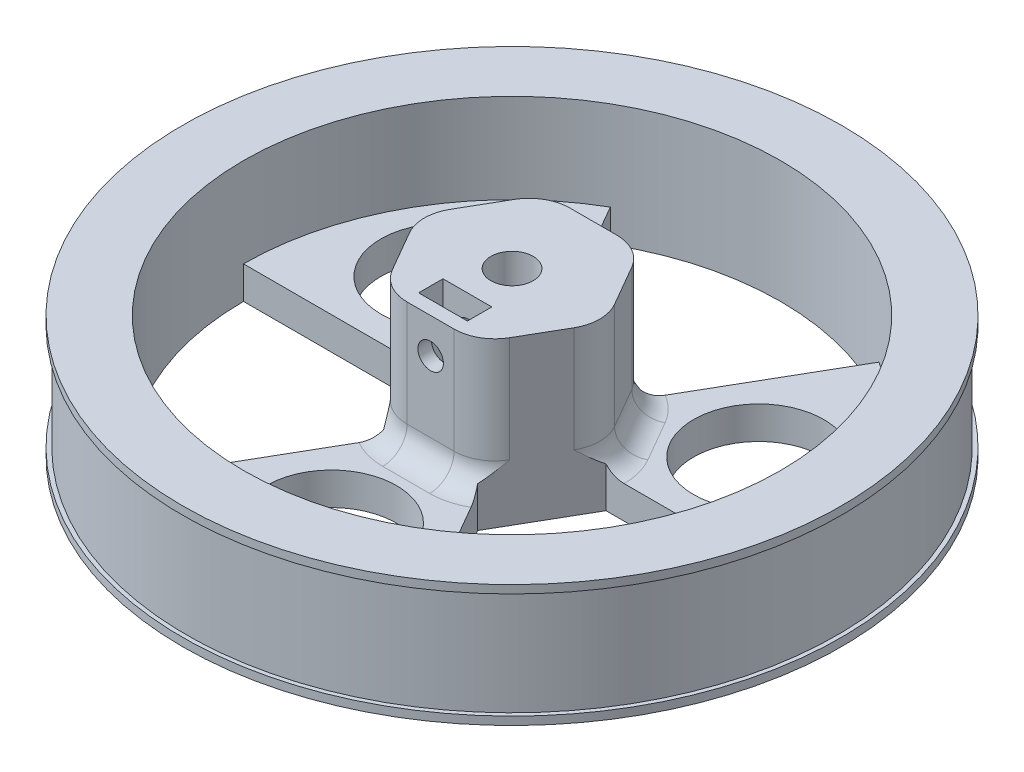
SolidWorks part; units mm, degrees
ref_plane "Front Plane" through (0, 0, 0) normal (0, 0, 1) x (1, 0, 0)
ref_plane "Top Plane" through (0, 0, 0) normal (0, 1, 0) x (1, 0, 0)
ref_plane "Right Plane" through (0, 0, 0) normal (1, 0, 0) x (0, 0, -1)
sketch "Sketch1" plane through (0, 0, 0) normal (0, 1, 0) x (1, 0, 0)
  line L0 (-1.4327, 1.3955) -> (1.21, 1.5925)
  circle A0 centre (0, 0) radius 40.5
  circle A1 centre (0, 0) radius 5
  arc A2 (1.21, 1.5925) -> (-1.4327, 1.3955) centre (0, 0) cw
extrude "Boss-Extrude16" add sketch "Sketch1" along normal blind 5 contours A0 A1 | A1 L0 A2 | A2 L0 region at (-39.3545, 0, 0) region at (-4.8586, 0, 0)
extrude "Boss-Extrude17" add sketch "Sketch1<23>" along normal blind 5 contours A1
sketch "Sketch1<23>" plane through (0, 0, 0) normal (0, 1, 0) x (1, 0, 0) same geometry as "Sketch1"
extrude "Cut-Extrude6" cut sketch "Sketch1<29>" along normal blind 15 contours A2 L0 region at (0.0099, 0, 0.1327)
sketch "Sketch1<29>" plane through (0, 0, 0) normal (0, 1, 0) x (1, 0, 0) same geometry as "Sketch1"
sketch "Sketch13" plane through (0, 5, 0) normal (0, 1, 0) x (1, 0, 0)
  line L0 (-3.828, 6.6303) -> (-19.0526, 33)
  line L1 (38.1051, 0) -> (19.0526, 33)
  line L2 (19.0526, 33) -> (-19.0526, 33)
  line L3 (-19.0526, 33) -> (-38.1051, 0)
  line L4 (-38.1051, 0) -> (-19.0526, -33)
  line L5 (-19.0526, -33) -> (19.0526, -33)
  line L6 (19.0526, -33) -> (38.1051, 0)
  line L7 (7.656, 0) -> (3.828, 6.6303)
  line L8 (3.828, 6.6303) -> (-3.828, 6.6303)
  line L9 (-3.828, 6.6303) -> (-7.656, 0)
  line L10 (-7.656, 0) -> (-3.828, -6.6303)
  line L11 (-3.828, -6.6303) -> (3.828, -6.6303)
  line L12 (3.828, -6.6303) -> (7.656, 0)
  line L13 (-7.656, 0) -> (-38.1051, 0)
  line L14 (-3.828, -6.6303) -> (-19.0526, -33)
  line L15 (3.828, -6.6303) -> (19.0526, -33)
  line L16 (7.656, 0) -> (38.1051, 0)
  line L17 (3.828, 6.6303) -> (19.0526, 33)
  line L18 (19.0526, 33) -> (3.828, 6.6303)
  circle A0 centre (0, 0) radius 33
  circle A1 centre (0, 0) radius 6.6303
extrude "Cut-Extrude7" cut sketch "Sketch13" against normal blind 5 contours L8 L17 L2 L0 region at (0, 5, -21.7812)
extrude "Cut-Extrude8" cut sketch "Sketch13<4>" against normal blind 5 contours L14 L10 L13 L4 region at (-18.8631, 5, 10.8906)
sketch "Sketch13<4>" plane through (0, 5, 0) normal (0, 1, 0) x (1, 0, 0) same geometry as "Sketch13"
extrude "Cut-Extrude9" cut sketch "Sketch13<5>" against normal blind 5 contours L16 L12 L15 L6 region at (18.8631, 5, 10.8906)
sketch "Sketch13<5>" plane through (0, 5, 0) normal (0, 1, 0) x (1, 0, 0) same geometry as "Sketch13"
extrude "Boss-Extrude19" add sketch "Sketch1<32>" along normal blind 5 contours A2 L0 region at (0.0099, 0, 0.1327)
sketch "Sketch1<32>" plane through (0, 0, 0) normal (0, 1, 0) x (1, 0, 0) same geometry as "Sketch1"
extrude "Cut-Extrude14" cut sketch "Sketch13<11>" against normal blind 1 contours L15 L11 L14 L5 | L17 L7 L16 L1 | L13 L9 L0 L3 region at (-18.8631, 5, -10.8906) region at (18.8631, 5, -10.8906) region at (0, 5, 21.7812)
sketch "Sketch13<11>" plane through (0, 5, 0) normal (0, 1, 0) x (1, 0, 0) same geometry as "Sketch13"
sketch "Sketch24" plane through (0, 5, 0) normal (0, 1, 0) x (1, 0, 0)
  circle A0 centre (0, -22.1926) radius 8
  circle A2 centre (19.2193, 11.0963) radius 8
  circle A3 centre (-19.2193, 11.0963) radius 8
extrude "Cut-Extrude15" cut sketch "Sketch24" against normal blind 4
extrude "Cut-Extrude16" cut sketch "Sketch24<2>" against normal blind 6
sketch "Sketch24<2>" plane through (0, 5, 0) normal (0, 1, 0) x (1, 0, 0) same geometry as "Sketch24"
sketch "Sketch30" plane through (0, 0, 0) normal (0, -1, 0) x (1, 0, 0)
  circle A0 centre (0, 0) radius 40
  circle A1 centre (0, 0) radius 33
extrude "Boss-Extrude21" add sketch "Sketch30" against normal blind 1
sketch "Sketch31" plane through (0, 5, 0) normal (0, 1, 0) x (1, 0, 0)
  line L1 (11.547, 0) -> (5.7735, 10)
  line L2 (5.7735, 10) -> (-5.7735, 10)
  line L3 (-5.7735, 10) -> (-11.547, 0)
  line L4 (-11.547, 0) -> (-5.7735, -10)
  line L5 (-5.7735, -10) -> (5.7735, -10)
  line L6 (5.7735, -10) -> (11.547, 0)
  circle A0 centre (0, 0) radius 10 construction
extrude "Boss-Extrude22" add sketch "Sketch31" along normal blind 15
sketch "Sketch33" plane through (0, 20, 0) normal (0, 1, 0) x (1, 0, 0)
  circle A0 centre (0, 0) radius 2.6
extrude "Cut-Extrude17" cut sketch "Sketch33" against normal blind 10
sketch "Sketch35" plane through (0, 20, 0) normal (0, 1, 0) x (1, 0, 0)
  line L0 (-3.1564, -8.3263) -> (2.8436, -8.3263)
  line L1 (-3.1564, -8.3263) -> (-3.1564, -5.3263)
  line L2 (2.8436, -8.3263) -> (2.8436, -5.3263)
  line L3 (-3.1564, -5.3263) -> (2.8436, -5.3263)
  line L4 (-3.1564, -8.3263) -> (2.8436, -5.3263) construction
  line L5 (2.8436, -8.3263) -> (-3.1564, -5.3263) construction
  point P1 (-0.1564, -6.8263)
extrude "Cut-Extrude18" cut sketch "Sketch35" against normal blind 10
sketch "Sketch36" plane through (0, 0, 5.3263) normal (0, 0, 1) x (1, 0, 0)
  circle A0 centre (0, 15.696) radius 1.5694
extrude "Cut-Extrude19" cut sketch "Sketch36" against normal blind 5 and the other way blind 17
sketch "Sketch37" plane through (0, 5, 0) normal (0, 1, 0) x (1, 0, 0)
  circle A0 centre (0, 0) radius 33
  circle A1 centre (0, 0) radius 40.5
extrude "Boss-Extrude23" add sketch "Sketch37" along normal blind 10
sketch "Sketch39" plane through (0, 0, 0) normal (0, 0, 1) x (1, 0, 0)
  line L0 (0, 0) -> (0, 39.678) construction
  line L1 (40, 1) -> (40.5, 1)
  line L2 (40, 1) -> (40, 14)
  line L3 (40, 14) -> (40.5, 14)
  line L4 (40.5, 1) -> (40.5, 14)
revolve "Cut-Revolve1" cut sketch "Sketch39" angle 360 about L0
extrude "Boss-Extrude25" add sketch "Sketch31<3>" against normal blind 5
sketch "Sketch31<3>" plane through (0, 5, 0) normal (0, 1, 0) x (1, 0, 0) same geometry as "Sketch31"
fillet "Fillet2" radius 5 6 edges at (5.7735, 12, 10) (-5.7735, 12, 10) (11.547, 12, 0) (5.7735, 12, -10) (-5.7735, 12, -10) (-11.547, 12, 0)
fillet "Fillet3" radius 3 9 edges at (5.3868, 4, 9.3301) (0, 4, 10) (-5.3868, 4, 9.3301) (-10.7735, 4, 0) (-8.6603, 4, -5) (-5.3868, 4, -9.3301) (10.7735, 4, 0) (8.6603, 4, -5) (5.3868, 4, -9.3301)
